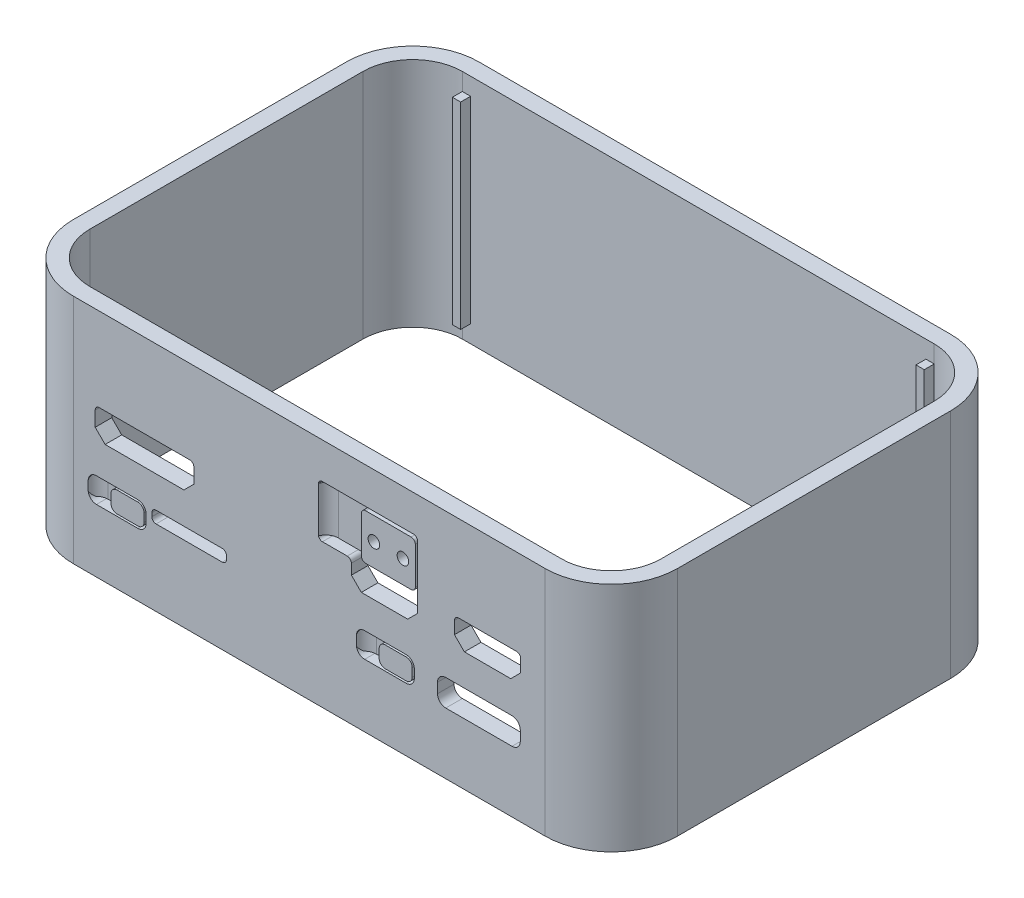
SolidWorks part; units mm, degrees
ref_plane "前视基准面" through (0, 0, 0) normal (0, 0, 1) x (1, 0, 0)
ref_plane "上视基准面" through (0, 0, 0) normal (0, 1, 0) x (1, 0, 0)
ref_plane "右视基准面" through (0, 0, 0) normal (1, 0, 0) x (0, 0, -1)
other "Configuration Table"
sketch "草图1" plane through (0, 0, 0) normal (0, 1, 0) x (1, 0, 0)
  line L0 (-33.3375, 28.4391) -> (35.6625, 28.4391)
  line L1 (-35.3375, 30.4391) -> (37.6625, 30.4391)
  line L2 (-35.3375, 30.4391) -> (-35.3375, -18.5609)
  line L3 (-35.3375, -18.5609) -> (37.6625, -18.5609)
  line L4 (37.6625, 30.4391) -> (37.6625, -18.5609)
  line L5 (35.6625, 28.4391) -> (35.6625, -16.5609)
  line L6 (-33.3375, -16.5609) -> (35.6625, -16.5609)
  line L7 (-33.3375, 28.4391) -> (-33.3375, -16.5609)
  dimension "D1" = 49
  dimension "D2" = 73
  dimension "D3" = 2
extrude "凸台-拉伸1" add sketch "草图1" along normal blind 28
fillet "圆角1" radius 6 4 edges at (-33.3375, 14, 16.5609) (-33.3375, 14, -28.4391) (35.6625, 14, -28.4391) (35.6625, 14, 16.5609)
fillet "圆角2" radius 8 4 edges at (37.6625, 14, 18.5609) (-35.3375, 14, 18.5609) (-35.3375, 14, -30.4391) (37.6625, 14, -30.4391)
sketch "草图2" plane through (0, 0, 18.5609) normal (0, 0, 1) x (1, 0, 0)
  line L0 (-31.5336, 12.4) -> (-43.7851, 12.4) construction
  line L1 (-27.3375, 28) -> (29.6625, 28) construction
  line L2 (6.2625, 17.35) -> (2.2625, 17.35)
  line L3 (-24.6875, 17.9) -> (-12.7699, 17.9)
  line L4 (-24.6875, 17.9) -> (-24.6875, 14.4)
  line L5 (-24.6875, 14.4) -> (-12.7699, 14.4)
  line L6 (-12.7699, 17.9) -> (-12.7699, 14.4)
  line L8 (6.2625, 17.35) -> (6.2625, 14.4)
  line L9 (6.2625, 14.4) -> (14.2625, 14.4)
  line L10 (14.2625, 23.65) -> (14.2625, 14.4)
  line L11 (18.7125, 17.6) -> (26.7125, 17.6)
  line L12 (18.7125, 17.6) -> (18.7125, 14.4)
  line L13 (18.7125, 14.4) -> (26.7125, 14.4)
  line L14 (26.7125, 17.6) -> (26.7125, 14.4)
  line L15 (-25.5375, 10.6) -> (-18.5375, 10.6)
  line L16 (-25.5375, 10.6) -> (-25.5375, 7.6)
  line L17 (-25.5375, 7.6) -> (-18.5375, 7.6)
  line L18 (-18.5375, 10.6) -> (-18.5375, 7.6)
  line L19 (-17.8375, 10.6) -> (-8.8375, 10.6)
  line L20 (-17.8375, 10.6) -> (-17.8375, 9.1638)
  line L21 (-17.8375, 9.1638) -> (-8.8375, 9.1638)
  line L22 (-8.8375, 10.6) -> (-8.8375, 9.1638)
  line L23 (6.8625, 10.6) -> (13.8625, 10.6)
  line L24 (6.8625, 10.6) -> (6.8625, 7.6)
  line L25 (6.8625, 7.6) -> (13.8625, 7.6)
  line L26 (13.8625, 10.6) -> (13.8625, 7.6)
  line L27 (16.6625, 10.6) -> (26.6625, 10.6)
  line L28 (16.6625, 10.6) -> (16.6625, 7.4)
  line L29 (16.6625, 7.4) -> (26.6625, 7.4)
  line L30 (26.6625, 10.6) -> (26.6625, 7.4)
  line L31 (2.2625, 17.35) -> (2.2625, 23.65)
  line L32 (2.2625, 23.65) -> (14.2625, 23.65)
  line L33 (-35.3375, 0) -> (-35.3375, 28) construction
  line L34 (37.6625, 28) -> (37.6625, 0) construction
  dimension "D1" = 15.6
  dimension "D2" = 1.8
  dimension "D3" = 2
  dimension "D4" = 7
  dimension "D5" = 9
  dimension "D6" = 3
  dimension "D7" = 3.5
  dimension "D8" = 12
  dimension "D9" = 6.3
  dimension "D10" = 3.2
  dimension "D11" = 8
  dimension "D12" = 10.65
  dimension "D13" = 9.25
  dimension "D14" = 10.95
  dimension "D15" = 10
  dimension "D16" = 11
  dimension "D17" = 3.2
  dimension "D18" = 23.4
  dimension "D19" = 9.8
  dimension "D20" = 17.5
  dimension "D21" = 23.8
extrude "切除-拉伸1" cut sketch "草图2" against normal up to next
chamfer "倒角1" distance 1.2 angle 45 6 edges at (26.7125, 14.4, 17.5609) (18.7125, 14.4, 17.5609) (14.2625, 14.4, 17.5609) (6.2625, 14.4, 17.5609) (-12.7699, 14.4, 17.5609) (-24.6875, 14.4, 17.5609)
fillet "圆角3" radius 0.5 12 edges at (26.7125, 17.6, 17.5609) (18.7125, 17.6, 17.5609) (6.2625, 17.35, 17.5609) (14.2625, 23.65, 17.5609) (2.2625, 23.65, 17.5609) (2.2625, 17.35, 17.5609) (-17.8375, 10.6, 17.5609) (-17.8375, 9.1638, 17.5609) (-8.8375, 9.1638, 17.5609) (-8.8375, 10.6, 17.5609) (-12.7699, 17.9, 17.5609) (-24.6875, 17.9, 17.5609)
fillet "圆角4" radius 1 12 edges at (13.8625, 7.6, 17.5609) (13.8625, 10.6, 17.5609) (-18.5375, 7.6, 17.5609) (-18.5375, 10.6, 17.5609) (16.6625, 7.4, 17.5609) (26.6625, 7.4, 17.5609) (26.6625, 10.6, 17.5609) (16.6625, 10.6, 17.5609) (6.8625, 7.6, 17.5609) (6.8625, 10.6, 17.5609) (-25.5375, 7.6, 17.5609) (-25.5375, 10.6, 17.5609)
sketch "草图3" plane through (0, 0, 16.5609) normal (0, 0, -1) x (-1, 0, 0)
  line L0 (-13.8625, 8.6) -> (-13.8625, 9.6) construction
  line L1 (-13.4826, 23.2) -> (-1.7421, 23.2)
  line L2 (-13.9826, 22.7) -> (-13.9826, 18.2)
  line L3 (-13.4826, 17.7) -> (-1.7421, 17.7)
  line L4 (-1.7421, 23.2) -> (-1.7421, 17.7)
  line L5 (-5.8046, 10.35) -> (-12.8619, 10.35)
  line L6 (-5.8046, 10.35) -> (-5.8046, 7.85)
  line L7 (-5.8046, 7.85) -> (-12.8619, 7.85)
  line L8 (-13.6119, 9.6) -> (-13.6119, 8.6)
  line L13 (-39.7707, 12.4) -> (-32.5793, 12.4) construction
  line L14 (-29.6625, 28) -> (-37.6625, 28) construction
  line L16 (18.5375, 8.6) -> (18.5375, 9.6) construction
  line L17 (26.3134, 10.35) -> (19.5375, 10.35)
  line L18 (26.3134, 10.35) -> (26.3134, 7.85)
  line L19 (26.3134, 7.85) -> (19.5375, 7.85)
  line L20 (18.7875, 9.6) -> (18.7875, 8.6)
  arc A2 (-12.8619, 10.35) -> (-13.6119, 9.6) centre (-12.8619, 9.6) ccw
  arc A3 (-12.8619, 7.85) -> (-13.6119, 8.6) centre (-12.8619, 8.6) cw
  arc A4 (-13.9826, 18.2) -> (-13.4826, 17.7) centre (-13.4826, 18.2) ccw
  arc A5 (-13.4826, 23.2) -> (-13.9826, 22.7) centre (-13.4826, 22.7) ccw
  arc A6 (19.5375, 10.35) -> (18.7875, 9.6) centre (19.5375, 9.6) ccw
  arc A7 (19.5375, 7.85) -> (18.7875, 8.6) centre (19.5375, 8.6) cw
  point P14 (-13.8625, 9.1)
  point P15 (-5.8046, 9.1)
  point P27 (18.7875, 7.85)
  point P34 (-13.6119, 10.35)
  point P37 (-13.6119, 7.85)
  point P40 (-13.9826, 17.7)
  point P43 (-13.9826, 23.2)
  dimension "D7" = 0.75
  dimension "D8" = 0.5
  dimension "D1" = 0.2506
  dimension "D2" = 5.5
  dimension "D3" = 15.6
  dimension "D4" = 5.3
  dimension "D5" = 2.05
  dimension "D6" = 0.25
extrude "凸台-拉伸2" add sketch "草图3" against normal blind 1
sketch "草图4" plane through (0, 0, 17.5609) normal (0, 0, 1) x (1, 0, 0)
  line L0 (7.2011, 10.35) -> (12.8619, 10.35) construction
  line L1 (12.8619, 7.85) -> (7.2011, 7.85) construction
  line L2 (-25.1989, 10.35) -> (-19.5375, 10.35) construction
  line L3 (-19.5375, 7.85) -> (-25.1989, 7.85) construction
  line L4 (13.4826, 23.2) -> (2.265, 23.2)
  line L5 (2.2625, 23.15) -> (2.2625, 17.85)
  line L6 (2.2855, 17.7) -> (13.4826, 17.7)
  line L7 (13.9826, 18.2) -> (13.9826, 22.7)
  line L8 (13.4826, 23.2) -> (7.9826, 23.2)
  line L10 (7.9826, 17.7) -> (13.4826, 17.7)
  line L11 (13.9826, 18.2) -> (13.9826, 22.7)
  line L12 (-25.1989, 7.85) -> (-19.5375, 7.85)
  line L13 (-18.7875, 8.6) -> (-18.7875, 9.6)
  line L14 (-19.5375, 10.35) -> (-25.1989, 10.35)
  line L15 (-25.5375, 9.6) -> (-25.5375, 8.6)
  line L16 (-22.0375, 7.85) -> (-19.5375, 7.85)
  line L17 (-18.7875, 8.6) -> (-18.7875, 9.6)
  line L18 (-19.5375, 10.35) -> (-22.0375, 10.35)
  line L20 (7.2011, 7.85) -> (12.8619, 7.85)
  line L21 (13.6119, 8.6) -> (13.6119, 9.6)
  line L22 (12.8619, 10.35) -> (7.2011, 10.35)
  line L24 (10.3619, 7.85) -> (12.8619, 7.85)
  line L25 (13.6119, 8.6) -> (13.6119, 9.6)
  line L26 (12.8619, 10.35) -> (10.3619, 10.35)
  line L28 (-22.7875, 9.6) -> (-22.7875, 8.6)
  line L29 (9.6119, 9.6) -> (9.6119, 8.6)
  line L30 (2.265, 23.2) -> (13.4826, 23.2) construction
  line L31 (7.4826, 22.7) -> (7.4826, 18.2)
  line L36 (6.8625, 9.6) -> (6.8625, 8.6)
  arc A0 (7.4826, 18.2) -> (7.9826, 17.7) centre (7.9826, 18.2) ccw
  arc A1 (7.9826, 23.2) -> (7.4826, 22.7) centre (7.9826, 22.7) ccw
  arc A2 (-22.7875, 8.6) -> (-22.0375, 7.85) centre (-22.0375, 8.6) ccw
  arc A3 (-22.0375, 10.35) -> (-22.7875, 9.6) centre (-22.0375, 9.6) ccw
  arc A4 (2.265, 23.2) -> (2.2625, 23.15) centre (2.7625, 23.15) ccw
  arc A5 (2.2625, 17.85) -> (2.2855, 17.7) centre (2.7625, 17.85) ccw
  arc A6 (13.4826, 17.7) -> (13.9826, 18.2) centre (13.4826, 18.2) ccw
  arc A7 (13.9826, 22.7) -> (13.4826, 23.2) centre (13.4826, 22.7) ccw
  arc A10 (13.4826, 17.7) -> (13.9826, 18.2) centre (13.4826, 18.2) ccw
  arc A11 (13.9826, 22.7) -> (13.4826, 23.2) centre (13.4826, 22.7) ccw
  arc A12 (-25.5375, 8.6) -> (-25.1989, 7.85) centre (-24.5375, 8.6) ccw
  arc A13 (-19.5375, 7.85) -> (-18.7875, 8.6) centre (-19.5375, 8.6) ccw
  arc A14 (-18.7875, 9.6) -> (-19.5375, 10.35) centre (-19.5375, 9.6) ccw
  arc A15 (-25.1989, 10.35) -> (-25.5375, 9.6) centre (-24.5375, 9.6) ccw
  arc A17 (-19.5375, 7.85) -> (-18.7875, 8.6) centre (-19.5375, 8.6) ccw
  arc A18 (-18.7875, 9.6) -> (-19.5375, 10.35) centre (-19.5375, 9.6) ccw
  arc A20 (6.8625, 8.6) -> (7.2011, 7.85) centre (7.8625, 8.6) ccw
  arc A21 (12.8619, 7.85) -> (13.6119, 8.6) centre (12.8619, 8.6) ccw
  arc A22 (13.6119, 9.6) -> (12.8619, 10.35) centre (12.8619, 9.6) ccw
  arc A23 (7.2011, 10.35) -> (6.8625, 9.6) centre (7.8625, 9.6) ccw
  arc A25 (12.8619, 7.85) -> (13.6119, 8.6) centre (12.8619, 8.6) ccw
  arc A26 (13.6119, 9.6) -> (12.8619, 10.35) centre (12.8619, 9.6) ccw
  arc A27 (9.6119, 8.6) -> (10.3619, 7.85) centre (10.3619, 8.6) ccw
  arc A28 (10.3619, 10.35) -> (9.6119, 9.6) centre (10.3619, 9.6) ccw
  point P56 (7.4826, 23.2)
  point P59 (-22.7875, 7.85)
  point P62 (-22.7875, 10.35)
  point P65 (9.6119, 7.85)
  point P68 (9.6119, 10.35)
  dimension "D4" = 0.5
  dimension "D5" = 0.75
  dimension "D6" = 4
  dimension "D7" = 4
  dimension "D8" = 6.5
  dimension "D1" = 0
  dimension "D2" = 0
  dimension "D3" = 0
extrude "凸台-拉伸3" add sketch "草图4" along normal blind 1
sketch "草图5" plane through (0, 0, 18.5609) normal (0, 0, 1) x (1, 0, 0)
  circle A0 centre (8.9826, 20.45) radius 0.7
  circle A1 centre (12.4826, 20.45) radius 0.7
  dimension "D1" = 1.4
extrude "切除-拉伸2" cut sketch "草图5" against normal up to next
fillet "圆角5" radius 1.5 3 edges at (6.8625, 9.1, 17.5609) (-25.5375, 9.1, 17.5609) (2.2625, 20.5, 17.5609)
sketch "草图6" plane through (0, 0, 16.5609) normal (0, 0, -1) x (-1, 0, 0)
  line L0 (-13.6119, 8.6) -> (-13.6119, 9.6) construction
  line L1 (-12.8619, 10.35) -> (-10.3619, 10.35) construction
  line L2 (-9.6119, 9.6) -> (-9.6119, 8.6) construction
  line L3 (-10.3619, 7.85) -> (-12.8619, 7.85) construction
  line L4 (18.7875, 8.6) -> (18.7875, 9.6) construction
  line L5 (19.5375, 10.35) -> (22.0375, 10.35) construction
  line L6 (22.7875, 9.6) -> (22.7875, 8.6) construction
  line L7 (22.0375, 7.85) -> (19.5375, 7.85) construction
  line L8 (-13.6119, 8.6) -> (-13.6119, 9.6)
  line L9 (-12.8619, 10.35) -> (-10.3619, 10.35)
  line L10 (-9.6119, 9.6) -> (-9.6119, 8.6)
  line L11 (-10.3619, 7.85) -> (-12.8619, 7.85)
  line L12 (18.7875, 8.6) -> (18.7875, 9.6)
  line L13 (19.5375, 10.35) -> (22.0375, 10.35)
  line L14 (22.7875, 9.6) -> (22.7875, 8.6)
  line L15 (22.0375, 7.85) -> (19.5375, 7.85)
  arc A0 (-13.6119, 8.6) -> (-12.8619, 7.85) centre (-12.8619, 8.6) ccw construction
  arc A1 (-12.8619, 10.35) -> (-13.6119, 9.6) centre (-12.8619, 9.6) ccw construction
  arc A2 (-9.6119, 9.6) -> (-10.3619, 10.35) centre (-10.3619, 9.6) ccw construction
  arc A3 (-10.3619, 7.85) -> (-9.6119, 8.6) centre (-10.3619, 8.6) ccw construction
  arc A4 (18.7875, 8.6) -> (19.5375, 7.85) centre (19.5375, 8.6) ccw construction
  arc A5 (19.5375, 10.35) -> (18.7875, 9.6) centre (19.5375, 9.6) ccw construction
  arc A6 (22.7875, 9.6) -> (22.0375, 10.35) centre (22.0375, 9.6) ccw construction
  arc A7 (22.0375, 7.85) -> (22.7875, 8.6) centre (22.0375, 8.6) ccw construction
  arc A8 (-13.6119, 8.6) -> (-12.8619, 7.85) centre (-12.8619, 8.6) ccw
  arc A9 (-12.8619, 10.35) -> (-13.6119, 9.6) centre (-12.8619, 9.6) ccw
  arc A10 (-9.6119, 9.6) -> (-10.3619, 10.35) centre (-10.3619, 9.6) ccw
  arc A11 (-10.3619, 7.85) -> (-9.6119, 8.6) centre (-10.3619, 8.6) ccw
  arc A12 (18.7875, 8.6) -> (19.5375, 7.85) centre (19.5375, 8.6) ccw
  arc A13 (19.5375, 10.35) -> (18.7875, 9.6) centre (19.5375, 9.6) ccw
  arc A14 (22.7875, 9.6) -> (22.0375, 10.35) centre (22.0375, 9.6) ccw
  arc A15 (22.0375, 7.85) -> (22.7875, 8.6) centre (22.0375, 8.6) ccw
extrude "凸台-拉伸4" add sketch "草图6" along normal blind 0.9
sketch "草图7" plane through (0, 0, 16.5609) normal (0, 0, -1) x (-1, 0, 0)
  line L0 (-29.6625, 28) -> (-29.6625, 0) construction
  line L1 (-29.6625, 25.9) -> (-28.6625, 25.9)
  line L2 (-29.6625, 25.9) -> (-29.6625, 2.1)
  line L3 (-29.6625, 2.1) -> (-28.6625, 2.1)
  line L4 (-28.6625, 25.9) -> (-28.6625, 2.1)
  line L5 (27.3375, 0) -> (27.3375, 28) construction
  line L6 (27.3375, 25.9) -> (26.3375, 25.9)
  line L7 (27.3375, 25.9) -> (27.3375, 2.1)
  line L8 (27.3375, 2.1) -> (26.3375, 2.1)
  line L9 (26.3375, 25.9) -> (26.3375, 2.1)
  line L10 (-29.6625, 28) -> (27.3375, 28) construction
  line L11 (-29.6625, 0) -> (27.3375, 0) construction
  point P14 (0, 0)
  point P17 (0, 0)
  dimension "D1" = 2.1
  dimension "D2" = 2.1
  dimension "D3" = 1
extrude "凸台-拉伸5" add sketch "草图7" along normal blind 1.2
sketch "草图8" plane through (0, 0, -28.4391) normal (0, 0, 1) x (1, 0, 0)
  line L0 (-27.3375, 28) -> (-27.3375, 0) construction
  line L1 (-27.3375, 25.9) -> (-26.3375, 25.9)
  line L2 (-27.3375, 25.9) -> (-27.3375, 2.1)
  line L3 (-27.3375, 2.1) -> (-26.3375, 2.1)
  line L4 (-26.3375, 25.9) -> (-26.3375, 2.1)
  line L5 (-27.3375, 25.9) -> (-26.3375, 25.9) construction
  line L6 (-26.3375, 2.1) -> (-27.3375, 2.1) construction
  line L7 (-26.3375, 25.9) -> (-26.3375, 2.1) construction
  line L8 (28.6625, 25.9) -> (29.6625, 25.9) construction
  line L9 (29.6625, 25.9) -> (28.6625, 25.9)
  line L10 (29.6625, 25.9) -> (29.6625, 2.1)
  line L11 (29.6625, 2.1) -> (28.6625, 2.1)
  line L12 (28.6625, 25.9) -> (28.6625, 2.1)
  line L13 (29.6625, 0) -> (29.6625, 28) construction
  line L14 (29.6625, 2.1) -> (28.6625, 2.1) construction
  line L15 (28.6625, 2.1) -> (28.6625, 25.9) construction
extrude "凸台-拉伸6" add sketch "草图8" along normal blind 1.2
